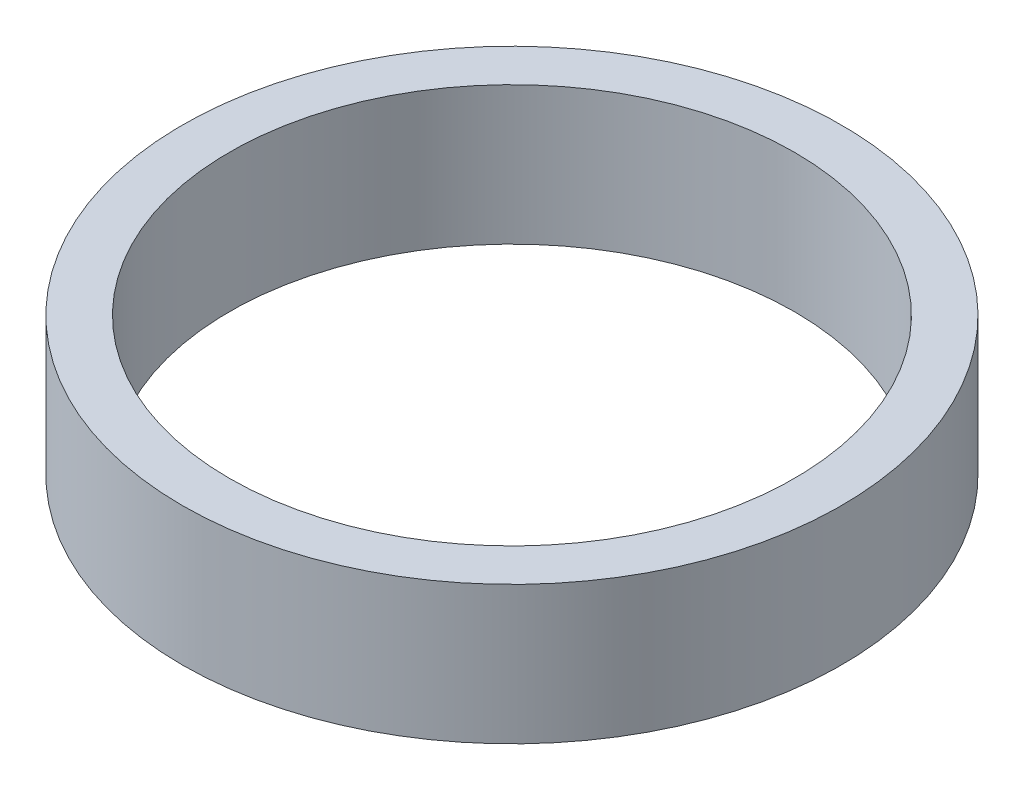
SolidWorks part; units mm, degrees
ref_plane "Front Plane" through (0, 0, 0) normal (0, 0, 1) x (1, 0, 0)
ref_plane "Top Plane" through (0, 0, 0) normal (0, 1, 0) x (1, 0, 0)
ref_plane "Right Plane" through (0, 0, 0) normal (1, 0, 0) x (0, 0, -1)
sketch "Sketch1" plane through (0, 0, 0) normal (0, 1, 0) x (1, 0, 0)
  circle A0 centre (0, 0) radius 52.5
  dimension "FLANGE_OD" = 105
extrude "Boss-Extrude1" add sketch "Sketch1" along normal blind 22
sketch "Sketch2" plane through (0, 0, 0) normal (0, 1, 0) x (1, 0, 0)
  circle A0 centre (0, 0) radius 45
  dimension "BORE_D" = 90
extrude "Cut-Extrude1" cut sketch "Sketch2" along normal through all
sketch "Sketch3" plane through (0, 22, 0) normal (0, 1, 0) x (1, 0, 0)
  circle A0 centre (0, 0) radius 24.1471 construction
  circle A1 centre (-24.1471, 0) radius 1.5
  dimension "BOLT_D" = 3
  dimension "BOLT_PCD" = 48.2942
extrude "Cut-Extrude2" cut sketch "Sketch3" against normal blind 21.5565 rebuild error yes
pattern_circular "CirPattern1" count 4 over 360 rebuild error yes
